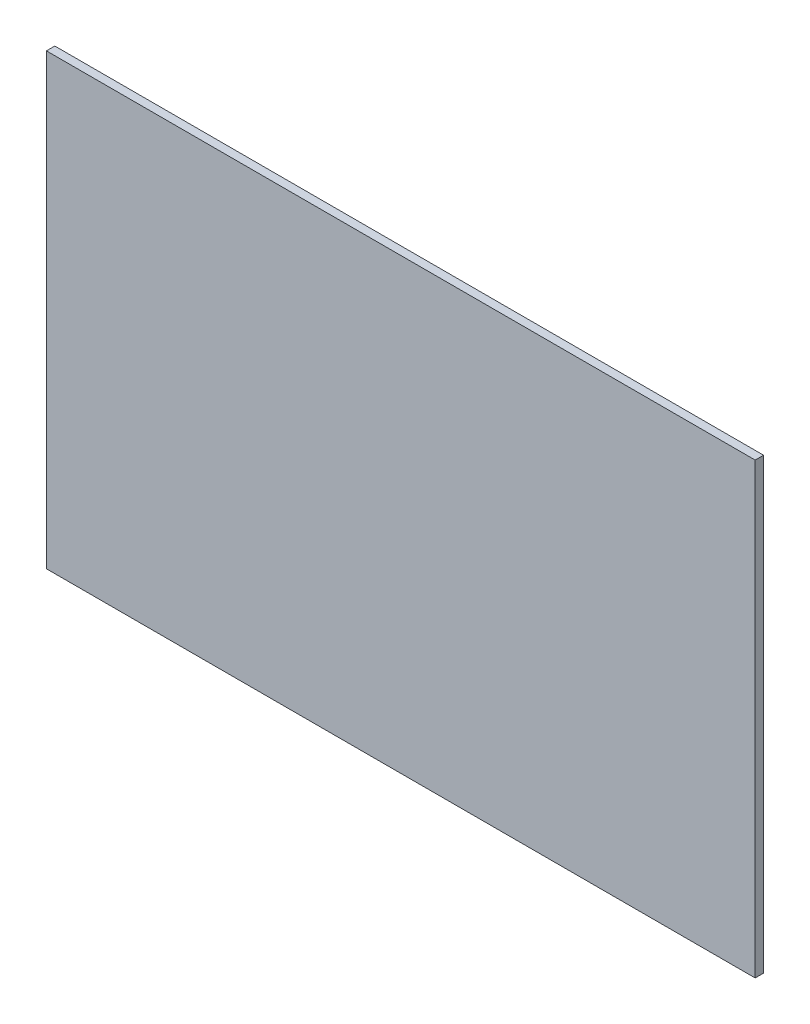
SolidWorks part; units mm, degrees
ref_plane "Alzado" through (0, 0, 0) normal (0, 0, 1) x (1, 0, 0)
ref_plane "Planta" through (0, 0, 0) normal (0, 1, 0) x (1, 0, 0)
ref_plane "Vista lateral" through (0, 0, 0) normal (1, 0, 0) x (0, 0, -1)
sketch "Croquis1" plane through (0, 0, 0) normal (0, 0, 1) x (1, 0, 0)
  line L1 (-183.8771, -134.785) -> (69.3458, -134.785)
  line L2 (-183.8771, -134.785) -> (-183.8771, 25.4643)
  line L3 (-183.8771, 25.4643) -> (69.3458, 25.4643)
  line L4 (69.3458, -134.785) -> (69.3458, 25.4643)
  line L5 (-183.8771, -134.785) -> (69.3458, 25.4643) construction
  line L6 (-183.8771, 25.4643) -> (69.3458, -134.785) construction
  point P0 (-57.2656, -54.6604)
  point P5 (-183.8771, -134.785)
  point P6 (69.3458, 25.4643)
extrude "Saliente-Extruir1" add sketch "Croquis1" along normal blind 3
